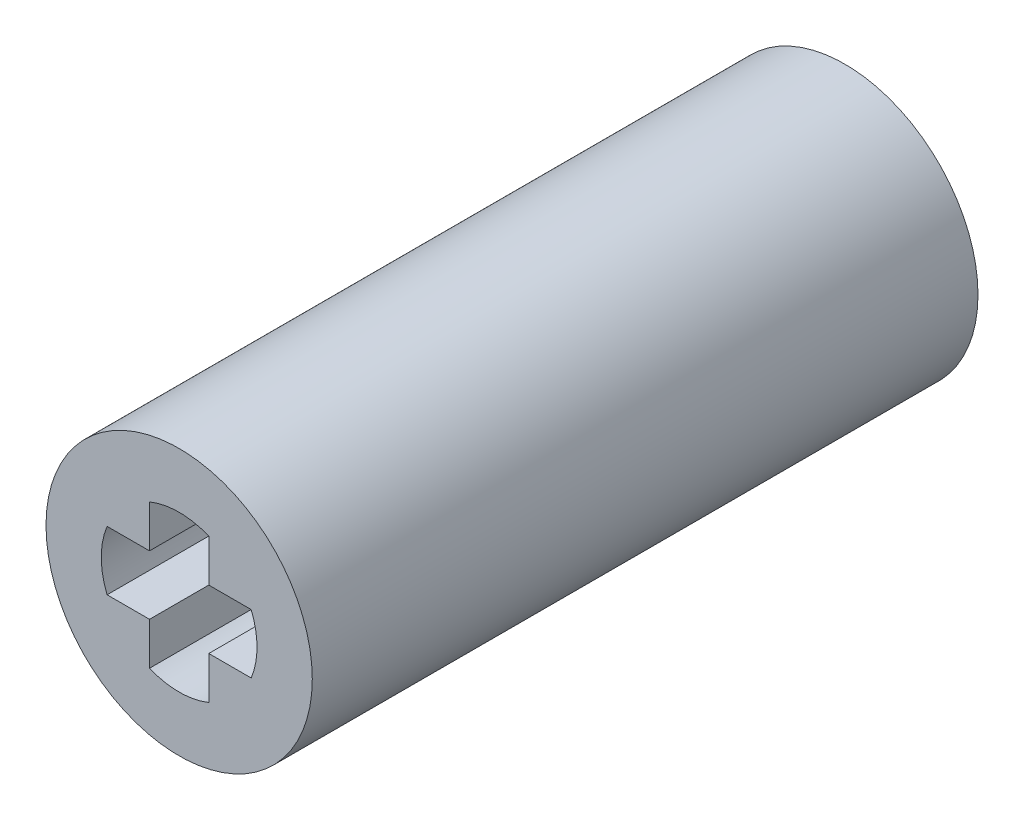
SolidWorks part; units mm, degrees
ref_plane "Front Plane" through (0, 0, 0) normal (0, 0, 1) x (1, 0, 0)
ref_plane "Top Plane" through (0, 0, 0) normal (0, 1, 0) x (1, 0, 0)
ref_plane "Right Plane" through (0, 0, 0) normal (1, 0, 0) x (0, 0, -1)
sketch "Sketch1" plane through (0, 0, 0) normal (0, 0, 1) x (1, 0, 0)
  line L0 (-0.89, 2.1641) -> (-0.89, -2.1641)
  line L2 (0.89, -2.1641) -> (0.89, 2.1641)
  line L4 (-1.118, 1) -> (1.118, 1)
  line L5 (-2.1641, 0.89) -> (2.1641, 0.89)
  line L7 (-2.1641, -0.89) -> (2.1641, -0.89)
  circle A0 centre (0, 0) radius 2.34
  circle A1 centre (0, 0) radius 1.5
  circle A2 centre (0, 0) radius 4
  dimension "D1" = 4.68
  dimension "D3" = 3
  dimension "D8" = 8
  dimension "D2" = 1.78
  dimension "D4" = 1
  dimension "D5" = 1.78
  dimension "D6" = 0.89
  dimension "D7" = 0.89
extrude "Boss-Extrude1" add sketch "Sketch1" along normal blind 10 contours A2 A0 | A1 L0 A0 L5 | A1 L5 A0 L2 | L4 A1 L5 L0 | L0 A1 L4 | L4 A1 L2 | L5 A1 L4 L2 | L2 A1 L7 | A1 L2 A0 L7 | A1 L7 A0 L0 | L7 A1 L0 region at (-1.3916, 1.3916, 0) region at (-0.9686, 1.0715, 0) region at (1.3916, 1.3916, 0) region at (-1.0283, 0.942, 0) region at (0.9686, 1.0715, 0) region at (-1.3916, -1.3916, 0) region at (1.0283, 0.942, 0) region at (-1.0011, -1.0011, 0) region at (1.3916, -1.3916, 0) region at (1.0011, -1.0011, 0) region at (-3.8869, 0, 0)
extrude "Boss-Extrude2" add sketch "Sketch1<3>" against normal blind 10 contours A2 A0 | A1 L2 A0 L7 | A1 L7 A0 L5 | A1 L5 A0 L2 | A1 L2 A0 L0 | A1 L0 A0 L5 | A1 L5 A0 L7 | A1 L7 A0 L0 | L4 A1 L2 | L2 A1 L0 L4 | L0 A1 L4 | A1 L0 A0 L2 region at (0, 1.8418, 0) region at (-1.3916, 1.3916, 0) region at (0, 1.2124, 0) region at (-0.9686, 1.0715, 0) region at (1.3916, 1.3916, 0) region at (-1.8418, 0, 0) region at (0.9686, 1.0715, 0) region at (1.8418, 0, 0) region at (-1.3916, -1.3916, 0) region at (0, -1.8418, 0) region at (1.3916, -1.3916, 0) region at (-3.8869, 0, 0)
sketch "Sketch1<3>" plane through (0, 0, 0) normal (0, 0, 1) x (1, 0, 0) same geometry as "Sketch1"
ref_axis "Axis1" through (0, 0, 10) along (0, 0, -1)
